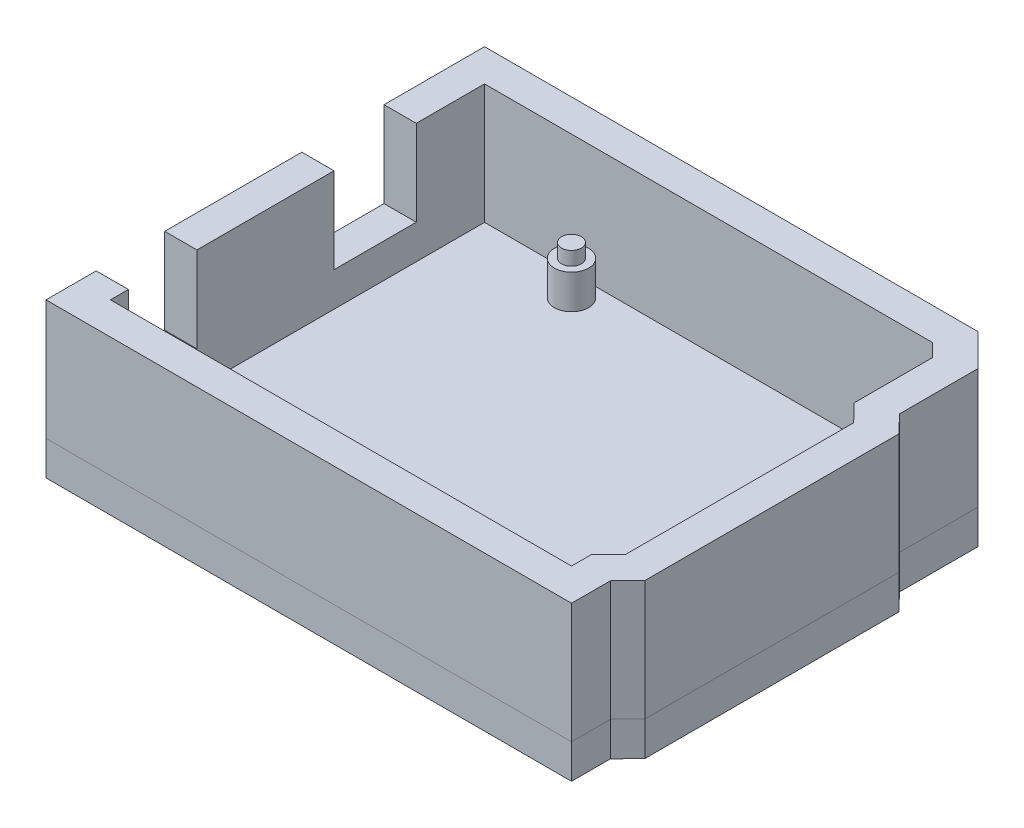
SolidWorks part; units mm, degrees
ref_plane "Front Plane" through (0, 0, 0) normal (0, 0, 1) x (1, 0, 0)
ref_plane "Top Plane" through (0, 0, 0) normal (0, 1, 0) x (1, 0, 0)
ref_plane "Right Plane" through (0, 0, 0) normal (1, 0, 0) x (0, 0, -1)
sketch "Sketch2" plane through (0, 0, 0) normal (0, 1, 0) x (1, 0, 0)
  line L0 (-53.4803, 37.7956) -> (11.0249, 37.7956)
  line L1 (11.0249, 37.7956) -> (12.5897, 36.2308)
  line L2 (12.5897, 36.2308) -> (12.5897, 24.8031)
  line L3 (12.5897, 24.8031) -> (15.0697, 22.2631)
  line L4 (15.0697, 22.2631) -> (15.0697, -10.5029)
  line L5 (15.0697, -10.5029) -> (12.5897, -13.0429)
  line L6 (12.5897, -13.0429) -> (12.5897, -15.5829)
  line L7 (12.5897, -15.5829) -> (-53.4803, -15.5829)
  line L8 (-53.4803, -15.5829) -> (-53.4803, 37.7956)
  line L9 (-58.7803, 43.0956) -> (13.2202, 43.0956)
  line L10 (13.2202, 43.0956) -> (17.8897, 38.4261)
  line L11 (17.8897, 38.4261) -> (17.8897, 26.9614)
  line L12 (17.8897, 26.9614) -> (20.3697, 24.4214)
  line L13 (20.3697, 24.4214) -> (20.3697, -12.6612)
  line L14 (20.3697, -12.6612) -> (17.8897, -15.2012)
  line L15 (17.8897, -15.2012) -> (17.8897, -20.8829)
  line L16 (17.8897, -20.8829) -> (-58.7803, -20.8829)
  line L17 (-58.7803, -20.8829) -> (-58.7803, 43.0956)
  circle A0 centre (-38.2103, 35.2171) radius 1.5875
  circle A1 centre (12.5579, 19.9653) radius 1.5875
  circle A2 centre (12.5897, -7.9629) radius 1.5875
  circle A3 centre (-39.5103, -13.0429) radius 1.5875
  dimension "D1" = 64.5052
  dimension "D2" = 2.2129
  dimension "D3" = 11.4277
  dimension "D4" = 3.5499
  dimension "D5" = 32.766
  dimension "D6" = 3.5499
  dimension "D7" = 2.54
  dimension "D8" = 66.07
  dimension "D9" = 53.3785
  dimension "D10" = 135
  dimension "D11" = 135.685
  dimension "D12" = 5.3
extrude "Boss-Extrude1" add sketch "Sketch2" along normal blind 5 contours L17 L16 L15 L14 L13 L12 L11 L10 L9 L7 L8 L0 L1 L2 L3 L4 L5 L6 | L8 L7 L6 L5 L4 L3 L2 L1 L0 A3 A2 A1 A0 region at (-19.6838, 0, -10.9923) region at (-22.7801, 0, -42.0778)
sketch "Sketch4" plane through (0, 5, 0) normal (0, 1, 0) x (1, 0, 0)
  line L0 (-53.4815, 37.799) -> (11.0238, 37.799)
  line L1 (11.0238, 37.799) -> (12.5885, 36.2342)
  line L2 (12.5885, 36.2342) -> (12.5885, 24.8065)
  line L3 (12.5885, 24.8065) -> (15.0685, 22.2665)
  line L4 (15.0685, 22.2665) -> (15.0685, -10.4995)
  line L5 (15.0685, -10.4995) -> (12.5885, -13.0395)
  line L6 (12.5885, -13.0395) -> (12.5885, -15.5795)
  line L7 (12.5885, -15.5795) -> (-53.4815, -15.5795)
  line L8 (-53.4815, -15.5795) -> (-53.4815, 37.799)
  line L9 (-58.7815, 43.099) -> (13.2191, 43.099)
  line L10 (13.2191, 43.099) -> (17.8885, 38.4295)
  line L11 (17.8885, 38.4295) -> (17.8885, 26.9649)
  line L12 (17.8885, 26.9649) -> (20.3685, 24.4249)
  line L13 (20.3685, 24.4249) -> (20.3685, -12.6578)
  line L14 (20.3685, -12.6578) -> (17.8885, -15.1978)
  line L15 (17.8885, -15.1978) -> (17.8885, -20.8795)
  line L16 (17.8885, -20.8795) -> (-58.7815, -20.8795)
  line L17 (-58.7815, -20.8795) -> (-58.7815, 43.099)
  line L18 (-54.0815, 38.399) -> (11.2723, 38.399)
  line L19 (11.2723, 38.399) -> (13.1885, 36.4827)
  line L20 (13.1885, 36.4827) -> (13.1885, 25.0509)
  line L21 (13.1885, 25.0509) -> (15.6685, 22.5109)
  line L22 (15.6685, 22.5109) -> (15.6685, -10.7438)
  line L23 (15.6685, -10.7438) -> (13.1885, -13.2838)
  line L24 (13.1885, -13.2838) -> (13.1885, -16.1795)
  line L25 (13.1885, -16.1795) -> (-54.0815, -16.1795)
  line L26 (-54.0815, -16.1795) -> (-54.0815, 38.399)
  circle A0 centre (-38.2115, 35.2205) radius 1.5875
  circle A1 centre (12.5567, 19.9688) radius 1.5875
  circle A2 centre (12.5885, -7.9595) radius 1.5875
  circle A3 centre (-39.5115, -13.0395) radius 1.5875
  dimension "D1" = 2.2129
  dimension "D2" = 11.4277
  dimension "D3" = 3.5499
  dimension "D4" = 32.766
  dimension "D5" = 3.5499
  dimension "D6" = 2.54
  dimension "D7" = 66.07
  dimension "D8" = 53.3785
  dimension "D9" = 135
  dimension "D10" = 135.685
  dimension "D11" = 0.6
extrude "Boss-Extrude3" add sketch "Sketch4" along normal blind 10 contours L9 L10 L11 L12 L13 L14 L15 L16 L17 | L18 L19 L20 L21 L22 L23 L24 L25 L26
sketch "Sketch5" plane through (0, 15, 0) normal (0, 1, 0) x (1, 0, 0)
  line L0 (-58.7815, -20.8795) -> (-58.7815, 43.099) construction
  line L6 (-54.0815, -3.561) -> (-58.7815, -3.561)
  line L7 (-54.0815, -16.1795) -> (-54.0815, 38.399) construction
  line L8 (-58.7815, 28.439) -> (-54.0815, 28.439)
  line L9 (-54.0815, -3.561) -> (-54.0815, -13.561)
  line L14 (-58.7815, 28.439) -> (-58.7815, 16.439)
  line L15 (-58.7815, 16.439) -> (-54.0815, 16.439)
  line L16 (-54.0815, 28.439) -> (-54.0815, 16.439)
  line L17 (-54.0815, -16.1795) -> (-54.0815, 38.399) construction
  line L21 (-54.0815, -3.561) -> (-54.0815, -13.561)
  line L22 (-54.0815, -13.561) -> (-58.7815, -13.561)
  line L26 (-54.0815, -3.561) -> (-54.0815, -13.561)
  line L28 (-54.0815, -3.561) -> (-54.0815, -13.561)
  line L31 (-58.7815, -3.561) -> (-58.7815, -13.561)
  line L32 (-58.7815, -3.561) -> (-54.0815, -3.561)
  line L33 (-58.7815, -3.561) -> (-58.7815, -13.561)
  line L34 (-58.7815, -13.561) -> (-54.0815, -13.561)
  line L35 (-54.0815, -3.561) -> (-54.0815, -13.561)
  line M14 (-58.7815, 43.099) -> (-58.7815, -20.8795)
  line M32 (-54.0815, -16.1795) -> (-54.0815, 38.399)
  dimension "D2" = 12
extrude "Cut-Extrude1" cut sketch "Sketch5" against normal blind 5 contours L22 L6 M32 M14 | L15 L8 M14 M32 region at (-56.4315, 15, 8.561) region at (-56.4315, 15, -22.439)
sketch "Sketch8" plane through (0, 15, 0) normal (0, 1, 0) x (1, 0, 0)
  line L52 (-58.7815, 28.439) -> (-54.0815, 28.439)
  line L57 (-54.0815, 28.439) -> (-54.0815, 38.399)
  line L58 (-54.0815, 38.399) -> (11.2723, 38.399)
  line L59 (11.2723, 38.399) -> (13.1885, 36.4827)
  line L60 (13.1885, 36.4827) -> (13.1885, 25.0509)
  line L61 (13.1885, 25.0509) -> (15.6685, 22.5109)
  line L62 (15.6685, 22.5109) -> (15.6685, -10.7438)
  line L63 (15.6685, -10.7438) -> (13.1885, -13.2838)
  line L64 (13.1885, -13.2838) -> (13.1885, -16.1795)
  line L65 (13.1885, -16.1795) -> (-54.0815, -16.1795)
  line L66 (-54.0815, -16.1795) -> (-54.0815, -13.561) construction
  line L67 (-54.0815, -16.1795) -> (-54.0815, 38.399) construction
  line L68 (-54.0815, -16.1795) -> (-54.0815, -13.561)
  line L69 (-54.0815, -13.561) -> (-58.7815, -13.561)
  line L70 (-58.7815, -13.561) -> (-58.7815, -20.8795)
  line L71 (-58.7815, -20.8795) -> (17.8885, -20.8795)
  line L72 (17.8885, -20.8795) -> (17.8885, -15.1978)
  line L73 (17.8885, -15.1978) -> (20.3685, -12.6578)
  line L74 (20.3685, -12.6578) -> (20.3685, 24.4249)
  line L75 (20.3685, 24.4249) -> (17.8885, 26.9649)
  line L76 (17.8885, 26.9649) -> (17.8885, 38.4295)
  line L77 (17.8885, 38.4295) -> (13.2191, 43.099)
  line L78 (13.2191, 43.099) -> (-58.7815, 43.099)
  line L79 (-58.7815, 43.099) -> (-58.7815, 28.439)
  line L81 (-58.7815, 16.439) -> (-54.0815, 16.439)
  line L82 (-58.7815, 16.439) -> (-58.7815, -3.561)
  line L83 (-58.7815, -3.561) -> (-54.0815, -3.561)
  line L84 (-54.0815, 16.439) -> (-54.0815, -3.561)
extrude "Boss-Extrude4" add sketch "Sketch8" along normal blind 7.5
sketch "Sketch9" plane through (0, 5, 0) normal (0, 1, 0) x (1, 0, 0)
  circle A0 centre (-38.2103, 35.2171) radius 2.5
  circle A1 centre (12.5579, 19.9653) radius 2.5
  circle A2 centre (12.5897, -7.9629) radius 2.5
  circle A3 centre (-39.5103, -13.0429) radius 2.5
  dimension "D1" = 5
  dimension "D2" = 5
  dimension "D3" = 5
  dimension "D4" = 5
extrude "Boss-Extrude5" add sketch "Sketch9" along normal blind 5
sketch "Sketch10" plane through (0, 10, 0) normal (0, 1, 0) x (1, 0, 0)
  circle A0 centre (-38.2103, 35.2171) radius 1.44
  circle A1 centre (12.5579, 19.9653) radius 1.425
  circle A2 centre (12.5897, -7.9629) radius 1.425
  circle A3 centre (-39.5103, -13.0429) radius 1.425
  dimension "D1" = 2.88
  dimension "D2" = 2.85
  dimension "D3" = 2.85
  dimension "D4" = 2.85
extrude "Boss-Extrude6" add sketch "Sketch10" along normal blind 2
